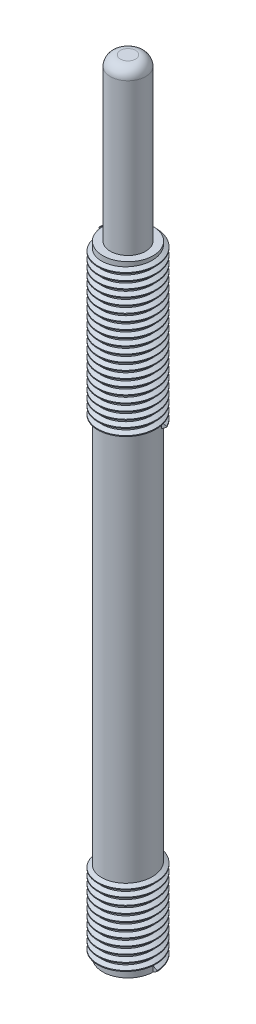
SolidWorks part; units mm, degrees
ref_plane "Front Plane" through (0, 0, 0) normal (0, 0, 1) x (1, 0, 0)
ref_plane "Top Plane" through (0, 0, 0) normal (0, 1, 0) x (1, 0, 0)
ref_plane "Right Plane" through (0, 0, 0) normal (1, 0, 0) x (0, 0, -1)
sketch "Sketch1" plane through (0, 0, 0) normal (0, 0, 1) x (1, 0, 0)
  line L0 (0, 38.75) -> (0, -38.75)
  line L1 (0, -38.75) -> (-2.5, -38.75)
  line L2 (-2.5, -38.75) -> (-2.5, 22.75)
  line L3 (0, 38.75) -> (-1.75, 38.75)
  line L4 (-1.75, 38.75) -> (-1.75, 22.75)
  line L5 (-1.75, 22.75) -> (-2.5, 22.75)
  point P4 (0, 0)
  dimension "D1" = 77.5
revolve "Revolve1" add sketch "Sketch1" angle 360 about L0
thread "Thread1" pitch 0.7 method extrude profile "Thread Profile1" start angle 0, offset 0, length 8, pitch 0.7, diameter 5
ref_plane "Plane1" through (2.5, -38.75, 0) normal (0, 0, 1) x (1, 0, 0)
sketch "Thread Profile1" plane through (2.5, -38.75, 0) normal (0, 0, 1) x (1, 0, 0)
  line L0 (0, 0) -> (0, 0.7) construction
  line L1 (0, 0) -> (0.3789, 0.2187)
  line L2 (0.3789, 0.2187) -> (0.3789, 0.3062)
  line L3 (0.3789, 0.3062) -> (0, 0.525)
  line L4 (0.3789, 0.2625) -> (0, 0.2625) construction
  line L11 (0, 0) -> (0, 0.525)
  point P2 (0, 0)
  dimension "Pitch" = 0.7
  dimension "Profile_Angle" = 60
  dimension "Profile_Land" = 0.0875
  dimension "Profile_Height" = 0.3789
thread "Thread2" pitch 0.7 method extrude profile "Thread Profile2" start angle 0, offset 0, length 15, pitch 0.7, diameter 5
ref_plane "Plane2" through (-2.5, 22.75, 0) normal (0, 0, 1) x (-1, 0, 0)
sketch "Thread Profile2" plane through (-2.5, 22.75, 0) normal (0, 0, 1) x (-1, 0, 0)
  line L0 (0, 0) -> (0, 0.7) construction
  line L1 (0, 0) -> (0.3789, 0.2187)
  line L2 (0.3789, 0.2187) -> (0.3789, 0.3062)
  line L3 (0.3789, 0.3062) -> (0, 0.525)
  line L4 (0.3789, 0.2625) -> (0, 0.2625) construction
  line L11 (0, 0) -> (0, 0.525)
  point P2 (0, 0)
  dimension "Pitch" = 0.7
  dimension "Profile_Angle" = 60
  dimension "Profile_Land" = 0.0875
  dimension "Profile_Height" = 0.3789
fillet "Fillet1" radius 1 1 edges at (0, 38.75, 1.75)
